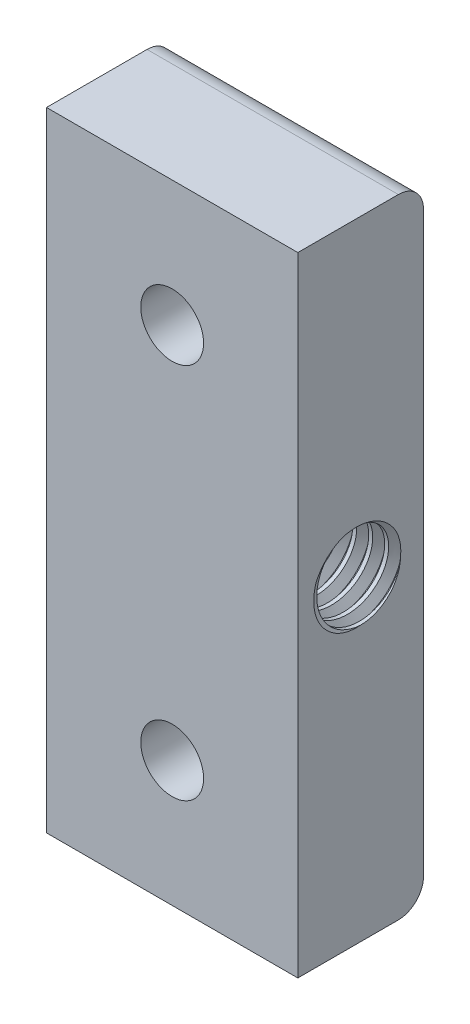
SolidWorks part; units mm, degrees
ref_plane "Front Plane" through (0, 0, 0) normal (0, 0, 1) x (1, 0, 0)
ref_plane "Top Plane" through (0, 0, 0) normal (0, 1, 0) x (1, 0, 0)
ref_plane "Right Plane" through (0, 0, 0) normal (1, 0, 0) x (0, 0, -1)
sketch "Sketch1" plane through (0, 0, 0) normal (0, 0, 1) x (1, 0, 0)
  line L1 (10, 25) -> (-10, 25)
  line L2 (10, 25) -> (10, -25)
  line L3 (10, -25) -> (-10, -25)
  line L4 (-10, 25) -> (-10, -25)
  line L5 (10, 25) -> (-10, -25) construction
  line L6 (10, -25) -> (-10, 25) construction
  circle A0 centre (0, 15) radius 2.5
  circle A1 centre (0, -15) radius 2.5
  point P0 (0, 0)
  point P10 (0, -25)
  dimension "D3" = 5
  dimension "D4" = 5
  dimension "D1" = 50
  dimension "D2" = 20
  dimension "D5" = 10
  dimension "D6" = 10
  dimension "D7" = 10
  dimension "D8" = 10
extrude "Boss-Extrude1" add sketch "Sketch1" along normal blind 10
sketch "Sketch2" plane through (0, 0, 0) normal (1, 0, 0) x (0, 0, -1)
  line L0 (0, 25) -> (0, -25) construction
  line L2 (-10, 25) -> (0, 25) construction
  circle A0 centre (-5, 0) radius 3.175
  dimension "D1" = 6.35
  dimension "D2" = 5
  dimension "D3" = 25
extrude "Cut-Extrude1" cut sketch "Sketch2" against normal blind 10 and the other way blind 10
fillet "Fillet1" radius 2 2 edges at (0, -25, 0) (0, 25, 0)
thread "Thread1" pitch 1.27 method cut profile "Thread Profile1" start angle 0, offset 0, length 30, pitch 1.27, diameter 6.35
ref_plane "Plane1" through (-10, 0, 1.825) normal (0, -1, 0) x (0, 0, -1)
sketch "Thread Profile1" plane through (-10, 0, 1.825) normal (0, -1, 0) x (0, 0, -1)
  line L0 (0, 0) -> (0, 1.27) construction
  line L1 (0, 0) -> (0.6874, 0.3969)
  line L2 (0.6874, 0.3969) -> (0.6874, 0.5556)
  line L3 (0.6874, 0.5556) -> (0, 0.9525)
  line L4 (0.6874, 0.4762) -> (0, 0.4762) construction
  line L11 (0, 0) -> (0, 0.9525)
  point P2 (0, 0)
  dimension "Pitch" = 1.27
  dimension "Profile_Angle" = 60
  dimension "Profile_Land" = 0.1588
  dimension "Profile_Height" = 0.6874
